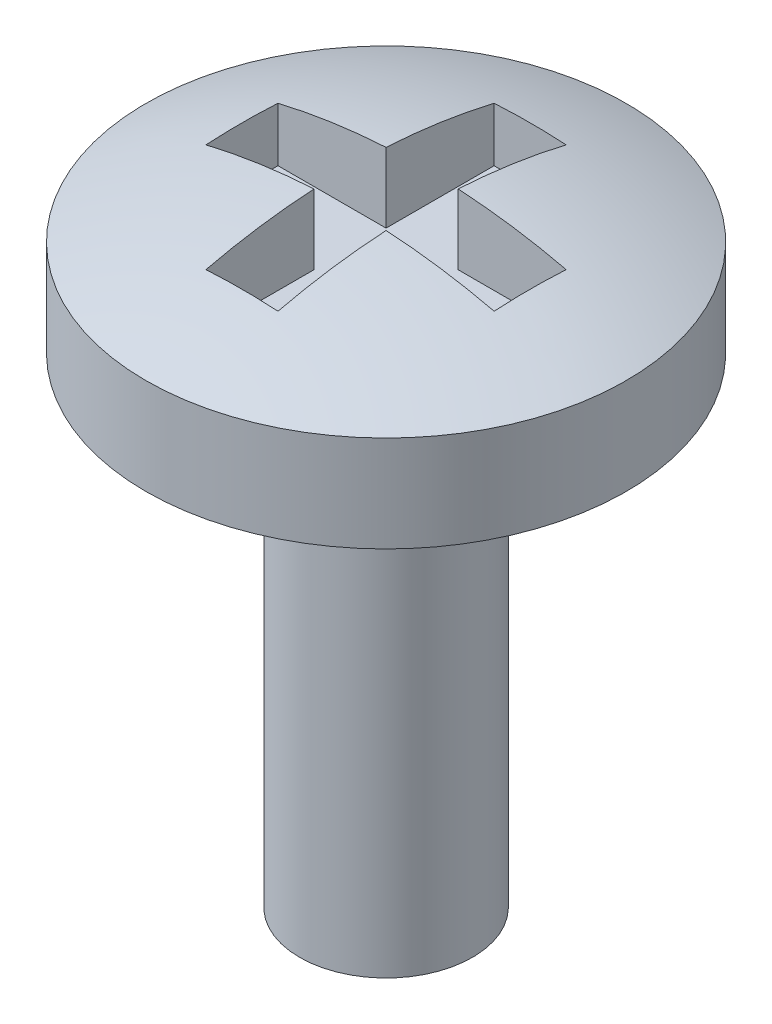
SolidWorks part; units mm, degrees
material "1023 Carbon Steel Sheet (SS)"
ref_plane "Front Plane" through (0, 0, 0) normal (0, 0, 1) x (1, 0, 0)
ref_plane "Top Plane" through (0, 0, 0) normal (0, 1, 0) x (1, 0, 0)
ref_plane "Right Plane" through (0, 0, 0) normal (1, 0, 0) x (0, 0, -1)
ref_plane "Top Plane1" through (0, 6.5, 0) normal (0, 1, 0) x (1, 0, 0)
sketch "Sketch1" plane through (0, 0, 0) normal (0, 1, 0) x (1, 0, 0)
  circle A0 centre (0, 0) radius 0.9
  dimension "D1" = 1.8
extrude "Boss-Extrude1" add sketch "Sketch1" along normal blind 5
sketch "Sketch2" plane through (0, 5, 0) normal (0, 1, 0) x (1, 0, 0)
  circle A0 centre (0, 0) radius 2.5
  dimension "D1" = 5
extrude "Boss-Extrude2" add sketch "Sketch2" along normal blind 1
dome "Dome1" faces to dome 1 distance 0.5 reverse direction no elliptical dome no face at (0, 6, 2.5) parameters "D1"=0.5
sketch "Sketch3" plane through (0, 6.5, 0) normal (0, 1, 0) x (1, 0, 0)
  line L0 (-2.5, 0) -> (2.5, 0) construction
  line L1 (0, 2.5) -> (0, -2.5) construction
  line L2 (-1.5, 0.375) -> (1.5, -0.375) construction
  line L3 (-1.5, 0.375) -> (1.5, 0.375)
  line L4 (-1.5, 0.375) -> (-1.5, -0.375)
  line L5 (-1.5, -0.375) -> (1.5, -0.375)
  line L6 (1.5, 0.375) -> (1.5, -0.375)
  line L7 (0.375, 1.5) -> (-0.375, -1.5) construction
  line L8 (-0.375, 1.5) -> (0.375, 1.5)
  line L9 (-0.375, 1.5) -> (-0.375, -1.5)
  line L10 (-0.375, -1.5) -> (0.375, -1.5)
  line L11 (0.375, 1.5) -> (0.375, -1.5)
  circle A0 centre (0, 0) radius 2.5 construction
  dimension "D1" = 1.5
  dimension "D2" = 1.5
  dimension "D3" = 0.75
  dimension "D4" = 0.75
extrude "Cut-Extrude1" cut sketch "Sketch3" against normal blind 0.75 contours L9 L3 L4 L5 | L11 L3 L9 L5 | L11 L8 L9 L3 | L3 L11 L5 L6 | L11 L5 L9 L10 region at (-0.9375, 6.5, 0) region at (0, 6.5, -0.9375) region at (0, 6.5, 0) region at (0.9375, 6.5, 0) region at (0, 6.5, 0.9375)
